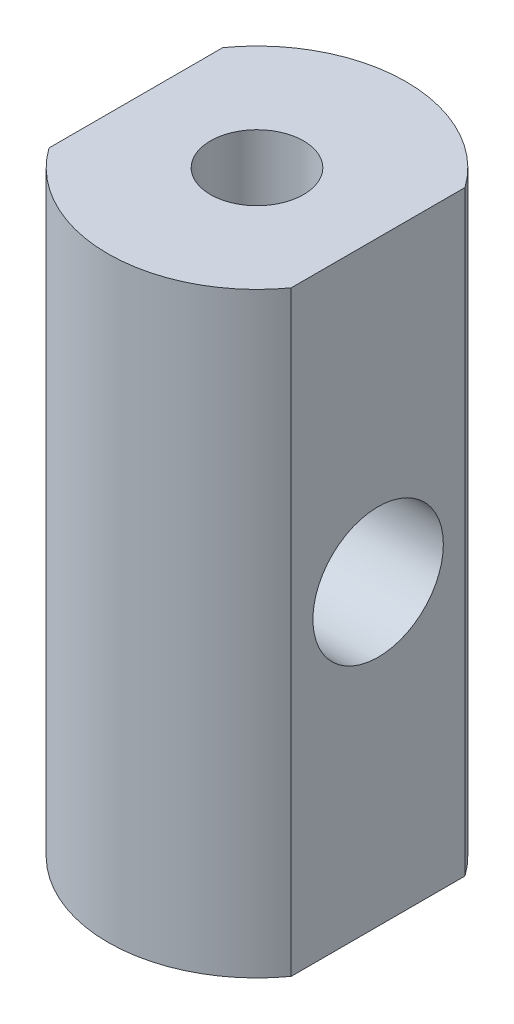
SolidWorks part; units mm, degrees
ref_plane "Front Plane" through (0, 0, 0) normal (0, 0, 1) x (1, 0, 0)
ref_plane "Top Plane" through (0, 0, 0) normal (0, 1, 0) x (1, 0, 0)
ref_plane "Right Plane" through (0, 0, 0) normal (1, 0, 0) x (0, 0, -1)
other "Configuration Table"
sketch "草图1" plane through (0, 0, 0) normal (0, 1, 0) x (1, 0, 0)
  circle A0 centre (0, 0) radius 8
  dimension "D1" = 16
extrude "凸台-拉伸1" add sketch "草图1" along normal blind 32
sketch "草图4" plane through (0, 32, 0) normal (0, 1, 0) x (1, 0, 0)
  point P0 (0, 0)
hole_wizard "M6x1.0 螺纹孔1" positions "草图4" profile "草图3" tap size "M6x1.0" standard "ANSI Metric"
sketch "草图3" plane through (0, 32, 0) normal (1, 0, 0) x (0, 0, 1)
  line L0 (0, 0) -> (0, 7.5022)
  line L1 (0, 7.5022) -> (2.5, 6)
  line L2 (2.5, 6) -> (2.5, 0)
  line L5 (2.5, 0) -> (0, 0)
  line L10 (0, 7.5022) -> (-2.5, 6) construction
  line L11 (0, -6.35) -> (0, 107.95) construction
  dimension "螺纹孔钻头直径" = 5
  dimension "螺纹孔钻头深度" = 6
  dimension "导头角度" = 118
cosmetic thread "孔螺纹线3" parameters "D1"=7, "D2"=6
sketch "草图7" plane through (0, 0, 0) normal (0, -1, 0) x (-1, 0, 0)
  point P0 (0, 0)
hole_wizard "M6x1.0 螺纹孔2" positions "草图7" profile "草图6" tap size "M6x1.0" standard "ANSI Metric"
sketch "草图6" plane through (0, 0, 0) normal (1, 0, 0) x (0, 0, -1)
  line L0 (0, 0) -> (0, 7.5022)
  line L1 (0, 7.5022) -> (2.5, 6)
  line L2 (2.5, 6) -> (2.5, 0)
  line L5 (2.5, 0) -> (0, 0)
  line L10 (0, 7.5022) -> (-2.5, 6) construction
  line L11 (0, -6.35) -> (0, 107.95) construction
  dimension "螺纹孔钻头直径" = 5
  dimension "螺纹孔钻头深度" = 6
  dimension "导头角度" = 118
cosmetic thread "孔螺纹线2" parameters "D1"=12, "D2"=6
sketch "草图10" plane through (0, 0, 0) normal (0, 0, 1) x (1, 0, 0)
  line L0 (0, 0) -> (0, 32) construction
  line L1 (-8, 0) -> (8, 0) construction
  line L2 (8, 32) -> (-8, 32) construction
  line L3 (0, 16) -> (6.5, 16) construction
  line L18 (6.5, -1.5) -> (6.5, 33.5)
  line L19 (6.5, 33.5) -> (8, 33.5)
  line L20 (8, 0) -> (8, 32) construction
  line L21 (8, 33.5) -> (8, -1.5)
  line L22 (8, 0) -> (8, 32) construction
  line L23 (8, -1.5) -> (6.5, -1.5)
  line L24 (-8, 33.5) -> (-8, -1.5)
  line L25 (-6.5, 33.5) -> (-8, 33.5)
  line L26 (-6.5, -1.5) -> (-6.5, 33.5)
  line L27 (-8, -1.5) -> (-6.5, -1.5)
  point P11 (6.5, 16)
extrude "切除-拉伸2" cut sketch "草图10" against normal blind 10 and the other way blind 10
sketch "草图11" plane through (6.5, 0, 0) normal (1, 0, 0) x (0, 0, -1)
  line L0 (0, 24.5) -> (0, 7.5) construction
  point P2 (0, 0)
sketch "草图16" plane through (6.5, 0, 0) normal (1, 0, 0) x (0, 0, -1)
  line L0 (0, 24.5) -> (0, 7.5) construction
  point P0 (0, 16)
hole_wizard "M8x1.0 螺纹孔1" positions "草图16" profile "草图15" tap size "M8x1.0" standard "ANSI Metric" end condition through all
sketch "草图15" plane through (6.5, 16, 0) normal (0, 1, 0) x (0, 0, -1)
  line L0 (0, 0) -> (0, 13)
  line L1 (0, 13) -> (3.5, 13)
  line L2 (3.5, 13) -> (3.5, 0)
  line L5 (3.5, 0) -> (0, 0)
  line L11 (0, -6.35) -> (0, 107.95) construction
  dimension "通孔螺纹孔钻头直径" = 7
  dimension "通孔螺纹孔钻头深度" = 13
cosmetic thread "孔螺纹线4" parameters "D2"=8
